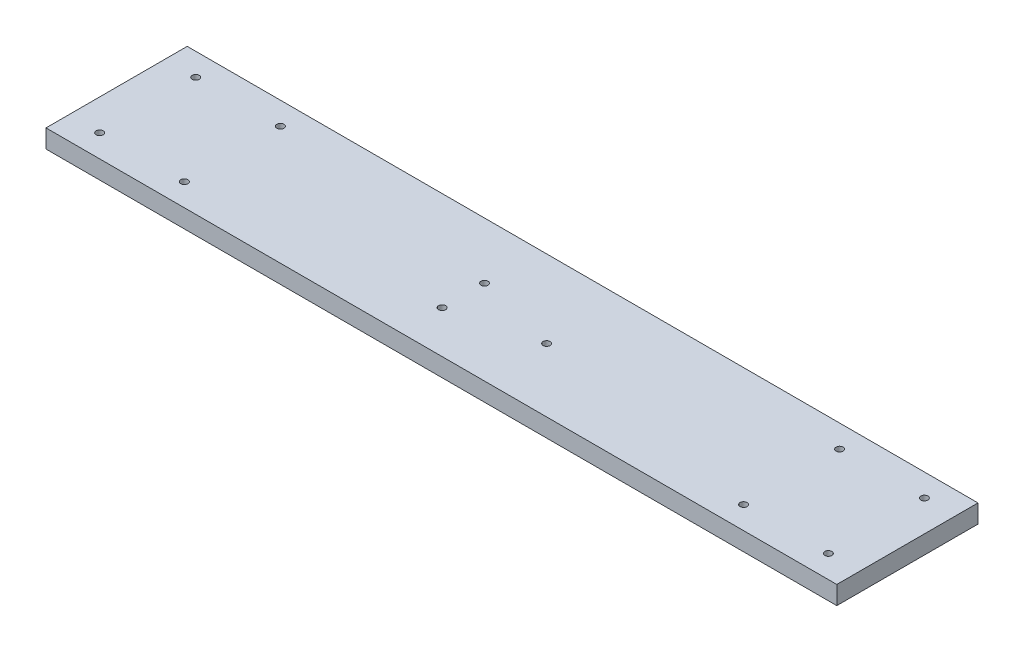
SolidWorks part; units mm, degrees
ref_plane "Front Plane" through (0, 0, 0) normal (0, 0, 1) x (1, 0, 0)
ref_plane "Top Plane" through (0, 0, 0) normal (0, 1, 0) x (1, 0, 0)
ref_plane "Right Plane" through (0, 0, 0) normal (1, 0, 0) x (0, 0, -1)
sketch "Sketch1" plane through (0, 0, 0) normal (0, 1, 0) x (1, 0, 0)
  line L1 (0, 0) -> (280, 0)
  line L2 (0, 0) -> (0, 50)
  line L3 (0, 50) -> (280, 50)
  line L4 (280, 0) -> (280, 50)
extrude "Boss-Extrude1" add sketch "Sketch1" along normal blind 6.5
sketch "Sketch2" plane through (0, 0, 0) normal (0, -1, 0) x (-1, 0, 0)
  circle A0 centre (-239, 42) radius 1.25
  circle A1 centre (-239, 8) radius 1.25
  circle A2 centre (-269, 8) radius 1.25
  circle A3 centre (-269, 42) radius 1.25
  circle A4 centre (-41, 42) radius 1.25
  circle A5 centre (-11, 42) radius 1.25
  circle A6 centre (-41, 8) radius 1.25
  circle A7 centre (-11, 8) radius 1.25
  circle A8 centre (-125.25, 30) radius 1.25
  circle A9 centre (-125.25, 15) radius 1.25
  circle A10 centre (-154.75, 22.5) radius 1.25
extrude "Cut-Extrude1" cut sketch "Sketch2" against normal through all
